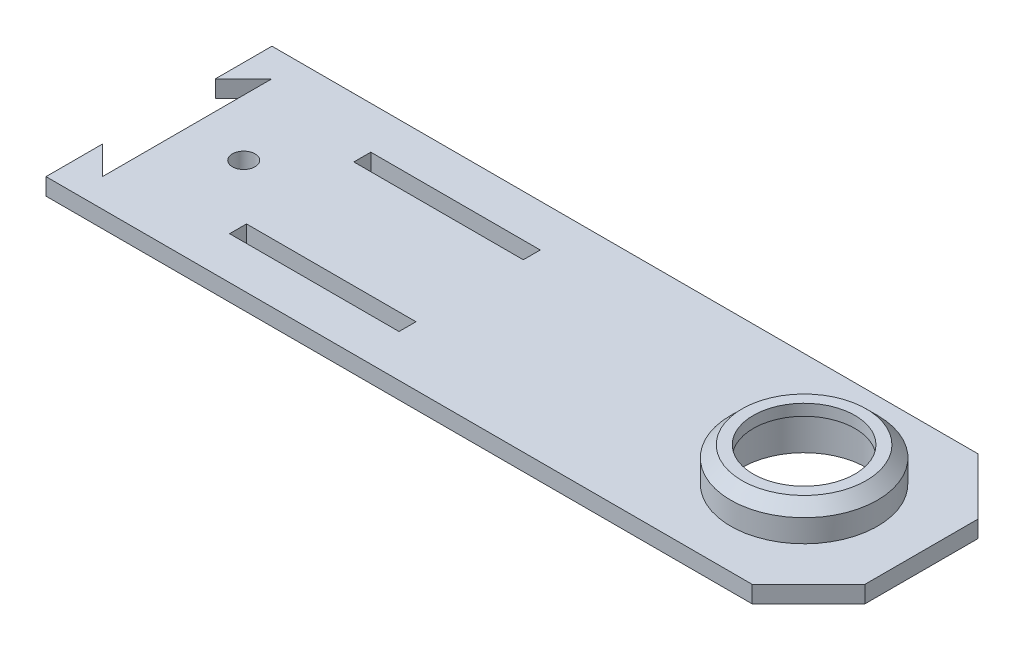
SolidWorks part; units mm, degrees
ref_plane "Alzado" through (0, 0, 0) normal (0, 0, 1) x (1, 0, 0)
ref_plane "Planta" through (0, 0, 0) normal (0, 1, 0) x (1, 0, 0)
ref_plane "Vista lateral" through (0, 0, 0) normal (1, 0, 0) x (0, 0, -1)
sketch "Croquis1" plane through (0, 0, 0) normal (0, 1, 0) x (1, 0, 0)
  line L0 (-67.5, 10) -> (-62.5, 15)
  line L1 (-67.5, -20) -> (67.5, -20)
  line L2 (-67.5, -20) -> (-67.5, -10)
  line L3 (-67.5, 20) -> (67.5, 20)
  line L4 (67.5, -20) -> (67.5, 20)
  line L5 (-67.5, -20) -> (67.5, 20) construction
  line L6 (-67.5, 20) -> (67.5, -20) construction
  line L7 (-62.5, 15) -> (-62.5, -15)
  line L8 (-62.5, -15) -> (-67.5, -10)
  line L9 (-67.5, 10) -> (-67.5, 20)
  line L11 (-42.5, 9.5) -> (-12.5, 9.5)
  line L12 (-42.5, 9.5) -> (-42.5, 12.5)
  line L13 (-42.5, 12.5) -> (-12.5, 12.5)
  line L14 (-12.5, 9.5) -> (-12.5, 12.5)
  line L15 (-42.5, 9.5) -> (-12.5, 12.5) construction
  line L16 (-42.5, 12.5) -> (-12.5, 9.5) construction
  line L17 (-42.5, -12.5) -> (-12.5, -12.5)
  line L18 (-42.5, -12.5) -> (-42.5, -9.5)
  line L19 (-42.5, -9.5) -> (-12.5, -9.5)
  line L20 (-12.5, -12.5) -> (-12.5, -9.5)
  line L21 (-42.5, -12.5) -> (-12.5, -9.5) construction
  line L22 (-42.5, -9.5) -> (-12.5, -12.5) construction
  circle A2 centre (46.714, 0) radius 11
  circle A3 centre (-52.5, 0) radius 2
  point P0 (0, 0)
  point P8 (-62.5, 0)
  point P11 (67.9468, 19.9537)
  point P12 (66.9088, -19.7356)
  point P13 (67.5, 19.3865)
  point P15 (66.8175, -19.5747)
  point P20 (-27.5, 11)
  point P28 (-27.5, -11)
  dimension "D7" = 22
  dimension "D11" = 10
  dimension "D12" = 4
  dimension "D1" = 40
  dimension "D2" = 135
  dimension "D3" = 45
  dimension "D4" = 20
  dimension "D5" = 30
  dimension "D8" = 30
  dimension "D9" = 3
  dimension "D10" = 40
  dimension "D13" = 12.5
  dimension "D14" = 12.5
extrude "Saliente-Extruir1" add sketch "Croquis1" along normal blind 3
sketch "Croquis2" plane through (0, 3, 0) normal (0, 1, 0) x (1, 0, 0)
  circle A0 centre (46.714, 0) radius 11
  circle A1 centre (46.714, 0) radius 13
  dimension "D1" = 2
extrude "Saliente-Extruir2" add sketch "Croquis2" along normal blind 4
sketch "Croquis3" plane through (0, 7, 0) normal (0, 1, 0) x (1, 0, 0)
  circle A0 centre (46.714, 0) radius 13
  circle A1 centre (46.714, 0) radius 9
  dimension "D1" = 18
extrude "Saliente-Extruir3" add sketch "Croquis3" along normal blind 2
chamfer "Chaflán1" distance 2 angle 45 1 edges at (46.714, 9, 13)
chamfer "Chaflán2" distance 10 angle 45 2 edges at (67.5, 1.5, -20) (67.5, 1.5, 20)
